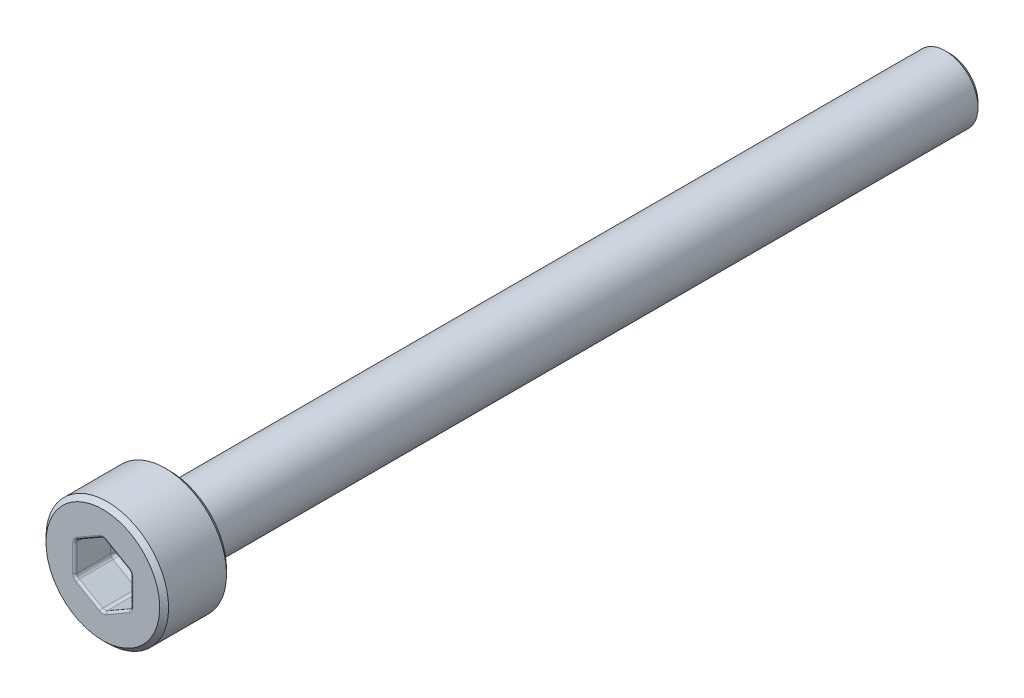
SolidWorks part; units mm, degrees
material "1.4000 (X6Cr13)"
ref_plane "Ebene vorne" through (0, 0, 0) normal (0, 0, 1) x (1, 0, 0)
ref_plane "Ebene oben" through (0, 0, 0) normal (0, 1, 0) x (1, 0, 0)
ref_plane "Ebene rechts" through (0, 0, 0) normal (1, 0, 0) x (0, 0, -1)
sketch "Skizze1" plane through (0, 0, 0) normal (1, 0, 0) x (0, 0, -1)
  line L0 (-21.9199, 0) -> (33.7608, 0) construction
  line L1 (0, 13.9907) -> (0, -9.4798) construction
  line L2 (-3, 0) -> (-3, 2.75)
  line L3 (-3, 2.75) -> (0, 2.75)
  line L4 (0, 2.75) -> (0, 1.465)
  line L5 (0, 1.465) -> (35, 1.465)
  line L6 (35, 1.465) -> (35, 0)
  line L7 (35, 0) -> (-3, 0)
  dimension "D1" = 2.93
  dimension "D2" = 3
  dimension "D3" = 5.5
  dimension "D4" = 35
revolve "Rotation1" add sketch "Skizze1" angle 360 about L0
sketch "Skizze2" plane through (0, 0, 3) normal (0, 0, 1) x (1, 0, 0)
  line L0 (0, 8.6995) -> (0, -7.3778) construction
  line L1 (1.25, -0.7217) -> (1.25, 0.7217)
  line L2 (1.25, 0.7217) -> (0, 1.4434)
  line L3 (0, 1.4434) -> (-1.25, 0.7217)
  line L4 (-1.25, 0.7217) -> (-1.25, -0.7217)
  line L5 (-1.25, -0.7217) -> (0, -1.4434)
  line L6 (0, -1.4434) -> (1.25, -0.7217)
  circle A0 centre (0, 0) radius 1.25 construction
  dimension "D1" = 2.5
extrude "Schnitt-Linear austragen1" cut sketch "Skizze2" against normal blind 1.8
chamfer "Fase1" distance 0.2 angle 45 3 edges at (2.75, 0, 3) (2.75, 0, 0) (1.465, 0, -35)
fillet "Verrundung1" radius 0.2 13 edges at (-0.625, -1.0825, 1.2) (-1.25, 0, 1.2) (-0.625, 1.0825, 1.2) (0.625, 1.0825, 1.2) (1.25, 0, 1.2) (0.625, -1.0825, 1.2) (-1.25, -0.7217, 2.1) (0, -1.4434, 2.1) (1.25, -0.7217, 2.1) (1.25, 0.7217, 2.1) (0, 1.4434, 2.1) (-1.25, 0.7217, 2.1) (1.465, 0, 0)
fillet "Verrundung2" radius 0.1 12 edges at (1.2232, -0.7062, 3) (0.625, -1.0825, 3) (0, -1.4124, 3) (-0.625, -1.0825, 3) (-1.2232, -0.7062, 3) (-1.25, 0, 3) (-1.2232, 0.7062, 3) (-0.625, 1.0825, 3) (0, 1.4124, 3) (0.625, 1.0825, 3) (1.2232, 0.7062, 3) (1.25, 0, 3)
ref_axis "Achse1" through (0, 0, -19.6323) along (0, 0, 1)
